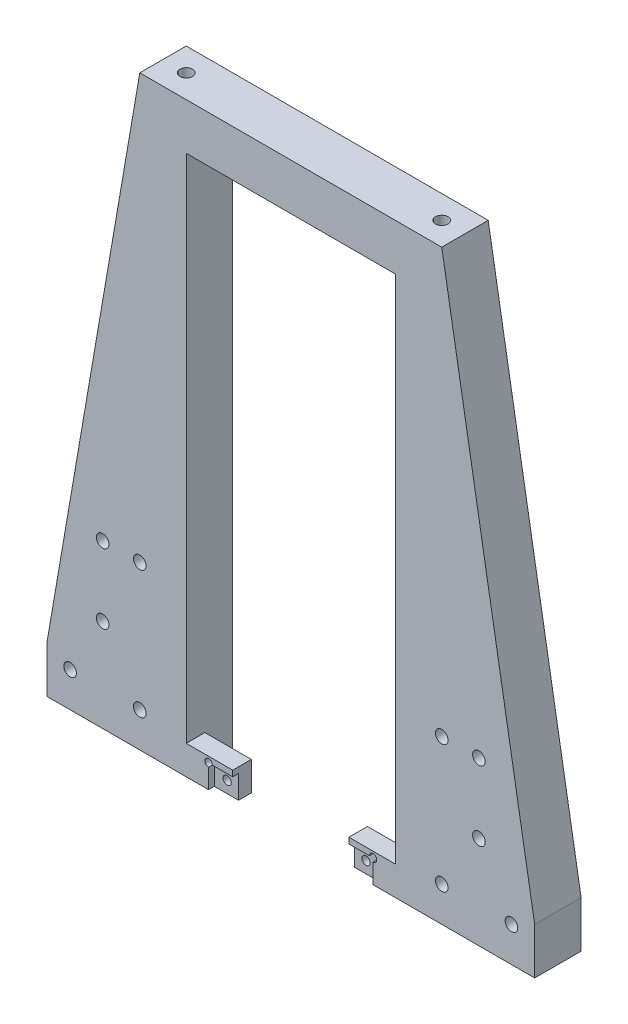
SolidWorks part; units mm, degrees
material "1060 Alloy"
ref_plane "Front Plane" through (0, 0, 0) normal (0, 0, 1) x (1, 0, 0)
ref_plane "Top Plane" through (0, 0, 0) normal (0, 1, 0) x (1, 0, 0)
ref_plane "Right Plane" through (0, 0, 0) normal (1, 0, 0) x (0, 0, -1)
sketch "Sketch1" plane through (0, 0, 0) normal (1, 0, 0) x (0, 0, -1)
  line L1 (0, 0) -> (12.7, 0)
  line L2 (0, 0) -> (0, -12.7)
  line L3 (0, -12.7) -> (12.7, -12.7)
  line L4 (12.7, 0) -> (12.7, -12.7)
  dimension "D1" = 12.7
  dimension "D2" = 12.7
extrude "Boss-Extrude1" add sketch "Sketch1" along normal blind 28.575
sketch "Sketch10" plane through (0, 0, 0) normal (0, 1, 0) x (1, 0, 0)
  line L1 (28.575, 12.7) -> (41.275, 12.7)
  line L2 (28.575, 12.7) -> (28.575, 0)
  line L3 (28.575, 0) -> (41.275, 0)
  line L4 (41.275, 12.7) -> (41.275, 0)
  dimension "D1" = 12.7
extrude "Boss-Extrude6" add sketch "Sketch10" against normal blind 160.3375
sketch "Sketch11" plane through (28.575, 0, 0) normal (-1, 0, 0) x (0, 0, 1)
  line L1 (0, -160.3375) -> (-5.08, -160.3375)
  line L2 (0, -160.3375) -> (0, -152.4)
  line L3 (0, -152.4) -> (-5.08, -152.4)
  line L4 (-5.08, -160.3375) -> (-5.08, -152.4)
  dimension "D1" = 5.08
  dimension "D2" = 7.9375
sketch "Sketch54" plane through (41.275, 0, 0) normal (1, 0, 0) x (0, 0, -1)
  line L0 (0, -160.3375) -> (0, 0) construction
  line L1 (12.7, -160.3375) -> (0, -160.3375)
  line L2 (12.7, -160.3375) -> (12.7, -147.6375)
  line L3 (12.7, -147.6375) -> (0, -147.6375)
  line L4 (0, -160.3375) -> (0, -147.6375)
  dimension "D1" = 12.7
extrude "Boss-Extrude10" add sketch "Sketch54" along normal blind 25.4
sketch "Sketch55" plane through (0, 0, 0) normal (0, 0, 1) x (1, 0, 0)
  line L0 (41.275, 0) -> (66.675, -147.6375)
  line L15 (28.575, -160.3375) -> (66.675, -160.3375)
  line L16 (66.675, -160.3375) -> (66.675, -147.6375)
  line L17 (66.675, -147.6375) -> (41.275, -147.6375)
  line L18 (41.275, -147.6375) -> (41.275, 0)
  line L19 (41.275, 0) -> (0, 0)
  line L20 (0, 0) -> (0, -12.7)
  line L21 (0, -12.7) -> (28.575, -12.7)
  line L22 (28.575, -12.7) -> (28.575, -160.3375)
  line L27 (28.575, -160.3375) -> (66.675, -160.3375)
  line L28 (66.675, -160.3375) -> (66.675, -147.6375)
  line L31 (41.275, 0) -> (0, 0)
  line L32 (0, 0) -> (0, -12.7)
  line L33 (0, -12.7) -> (28.575, -12.7)
  line L34 (28.575, -12.7) -> (28.575, -160.3375)
  dimension "D1" = 0
extrude "Boss-Extrude11" add sketch "Sketch55" against normal blind 12.7
hole_wizard "#8-32 Tapped Hole8" positions "Sketch57" profile "Sketch56" tap size "#8-32" standard "Ansi Inch"
sketch "Sketch57" plane through (0, 0, 0) normal (0, 1, 0) x (-1, 0, 0)
  line L0 (-34.925, -12.7) -> (-34.925, 0) construction
  line L1 (-41.275, -12.7) -> (0, -12.7) construction
  line L2 (-41.275, 0) -> (0, 0) construction
  line L4 (-41.275, 0) -> (-41.275, -12.7) construction
  point P0 (-34.925, -6.35)
  dimension "D1" = 6.35
cosmetic thread "Hole Thread11" parameters "D1"=8.3312, "D2"=4.1656
sketch "Sketch56" plane through (34.925, 0, -6.35) normal (1, 0, 0) x (0, 0, 1)
  line L0 (0, 0) -> (0, 11.7464)
  line L1 (0, 11.7464) -> (1.7272, 10.7086)
  line L2 (1.7272, 10.7086) -> (1.7272, 0)
  line L5 (1.7272, 0) -> (0, 0)
  line L10 (0, 11.7464) -> (-1.7272, 10.7086) construction
  line L11 (0, -6.35) -> (0, 107.95) construction
  dimension "Tap Drill Dia." = 3.4544
  dimension "Tap Drill Depth" = 10.7086
  dimension "Drill Angle" = 118
hole_wizard "#8-32 Tapped Hole11" positions "Sketch63" profile "Sketch62" tap size "#8-32" standard "Ansi Inch" end condition through all
sketch "Sketch63" plane through (0, 0, 0) normal (0, 0, 1) x (1, 0, 0)
  line L0 (28.575, -160.3375) -> (66.675, -160.3375) construction
  line L1 (66.675, -147.6375) -> (66.675, -160.3375) construction
  point P0 (41.275, -115.8875)
  point P1 (51.435, -134.9375)
  dimension "D1" = 25.4
  dimension "D2" = 15.24
  dimension "D3" = 44.45
  dimension "D4" = 25.4
cosmetic thread "Hole Thread19" parameters "D2"=4.1656
cosmetic thread "Hole Thread20" parameters "D2"=4.1656
sketch "Sketch62" plane through (41.275, -115.8875, 0) normal (1, 0, 0) x (0, -1, 0)
  line L0 (0, 0) -> (0, 12.7)
  line L1 (0, 12.7) -> (1.7272, 12.7)
  line L2 (1.7272, 12.7) -> (1.7272, 0)
  line L5 (1.7272, 0) -> (0, 0)
  line L11 (0, -6.35) -> (0, 107.95) construction
  dimension "Thru Tap Drill Dia." = 3.4544
  dimension "Thru Tap Drill Depth" = 12.7
hole_wizard "#8-32 Tapped Hole12" positions "Sketch65" profile "Sketch64" tap size "#8-32" standard "Ansi Inch" end condition through all
sketch "Sketch65" plane through (0, 0, -12.7) normal (0, 0, -1) x (-1, 0, 0)
  line L0 (-28.575, -160.3375) -> (-66.675, -160.3375) construction
  line L1 (-41.275, -150.8125) -> (-60.325, -150.8125) construction
  line L4 (-66.675, -147.6375) -> (-66.675, -160.3375) construction
  point P0 (-41.275, -150.8125)
  point P1 (-60.325, -150.8125)
  dimension "D1" = 9.525
  dimension "D2" = 19.05
  dimension "D3" = 25.4
cosmetic thread "Hole Thread21" parameters "D2"=4.1656
cosmetic thread "Hole Thread22" parameters "D2"=4.1656
sketch "Sketch64" plane through (41.275, -150.8125, -12.7) normal (1, 0, 0) x (0, 1, 0)
  line L0 (0, 0) -> (0, 12.7001)
  line L1 (0, 12.7001) -> (1.7272, 12.7001)
  line L2 (1.7272, 12.7001) -> (1.7272, 0)
  line L5 (1.7272, 0) -> (0, 0)
  line L11 (0, -6.35) -> (0, 107.95) construction
  dimension "Thru Tap Drill Dia." = 3.4544
  dimension "Thru Tap Drill Depth" = 12.7001
extrude "Boss-Extrude12" add sketch "Sketch11" along normal blind 12.7
sketch "Sketch68" plane through (0, 0, 0) normal (0, 0, 1) x (1, 0, 0)
  line L1 (15.875, -160.3375) -> (22.479, -160.3375)
  line L2 (15.875, -160.3375) -> (15.875, -153.9875)
  line L3 (15.875, -153.9875) -> (22.479, -153.9875)
  line L4 (22.479, -160.3375) -> (22.479, -153.9875)
  dimension "D1" = 6.35
  dimension "D2" = 6.604
extrude "Cut-Extrude4" cut sketch "Sketch68" against normal blind 1.5875
hole_wizard "#4-40 Tapped Hole3" positions "Sketch70" profile "Sketch69" tap size "#4-40" standard "Ansi Inch" end condition through all
sketch "Sketch70" plane through (0, 0, -1.5875) normal (0, 0, 1) x (1, 0, 0)
  point P0 (18.9872, -157.1723)
cosmetic thread "Hole Thread23" parameters "D2"=2.8448
sketch "Sketch69" plane through (18.9872, -157.1723, -1.5875) normal (1, 0, 0) x (0, -1, 0)
  line L0 (0, 0) -> (0, 11.1125)
  line L1 (0, 11.1125) -> (1.1303, 11.1125)
  line L2 (1.1303, 11.1125) -> (1.1303, 0)
  line L5 (1.1303, 0) -> (0, 0)
  line L11 (0, -6.35) -> (0, 107.95) construction
  dimension "Thru Tap Drill Dia." = 2.2606
  dimension "Thru Tap Drill Depth" = 11.1125
sketch "Sketch71" plane through (0, 0, 0) normal (0, 0, 1) x (1, 0, 0)
  circle A0 centre (22.479, -153.9875) radius 1.016
extrude "Cut-Extrude5" cut sketch "Sketch71" against normal blind 1.5875
hole_wizard "#8-32 Tapped Hole14" positions "Sketch77" profile "Sketch76" tap size "#8-32" standard "Ansi Inch"
sketch "Sketch77" plane through (0, -160.3375, 0) normal (0, -1, 0) x (1, 0, 0)
  circle A0 centre (34.925, -6.35) radius 1.7272 construction
  circle A1 centre (34.925, -6.35) radius 1.7272 construction
  point P0 (34.925, -6.35)
sketch "Sketch76" plane through (34.925, -160.3375, -6.35) normal (1, 0, 0) x (0, 0, -1)
  line L0 (0, 0) -> (0, 11.7464)
  line L1 (0, 11.7464) -> (1.7272, 10.7086)
  line L2 (1.7272, 10.7086) -> (1.7272, 0)
  line L5 (1.7272, 0) -> (0, 0)
  line L10 (0, 11.7464) -> (-1.7272, 10.7086) construction
  line L11 (0, -6.35) -> (0, 107.95) construction
  dimension "Tap Drill Dia." = 3.4544
  dimension "Tap Drill Depth" = 10.7086
  dimension "Drill Angle" = 118
cosmetic thread "Hole Thread25" parameters "D1"=8.3312, "D2"=4.1656
hole_wizard "#8-32 Tapped Hole13" positions "Sketch75" profile "Sketch74" tap size "#8-32" standard "Ansi Inch" end condition through all
sketch "Sketch75" plane through (0, 0, 0) normal (0, 0, 1) x (1, 0, 0)
  line L0 (22.479, -160.3375) -> (66.675, -160.3375) construction
  line L1 (66.675, -147.6375) -> (66.675, -160.3375) construction
  point P0 (51.435, -115.8875)
  dimension "D1" = 44.45
  dimension "D2" = 15.24
sketch "Sketch74" plane through (51.435, -115.8875, 0) normal (1, 0, 0) x (0, -1, 0)
  line L0 (0, 0) -> (0, 12.7001)
  line L1 (0, 12.7001) -> (1.7272, 12.7001)
  line L2 (1.7272, 12.7001) -> (1.7272, 0)
  line L5 (1.7272, 0) -> (0, 0)
  line L11 (0, -6.35) -> (0, 107.95) construction
  dimension "Thru Tap Drill Dia." = 3.4544
  dimension "Thru Tap Drill Depth" = 12.7001
cosmetic thread "Hole Thread24" parameters "D2"=4.1656
mirror "Mirror6" of "#8-32 Tapped Hole13", "#8-32 Tapped Hole14", "Boss-Extrude1", "Boss-Extrude6", "Boss-Extrude10", "Boss-Extrude11", "#8-32 Tapped Hole8", "#8-32 Tapped Hole11", "#8-32 Tapped Hole12", "Boss-Extrude12", "Cut-Extrude4", "#4-40 Tapped Hole3", "Cut-Extrude5"
